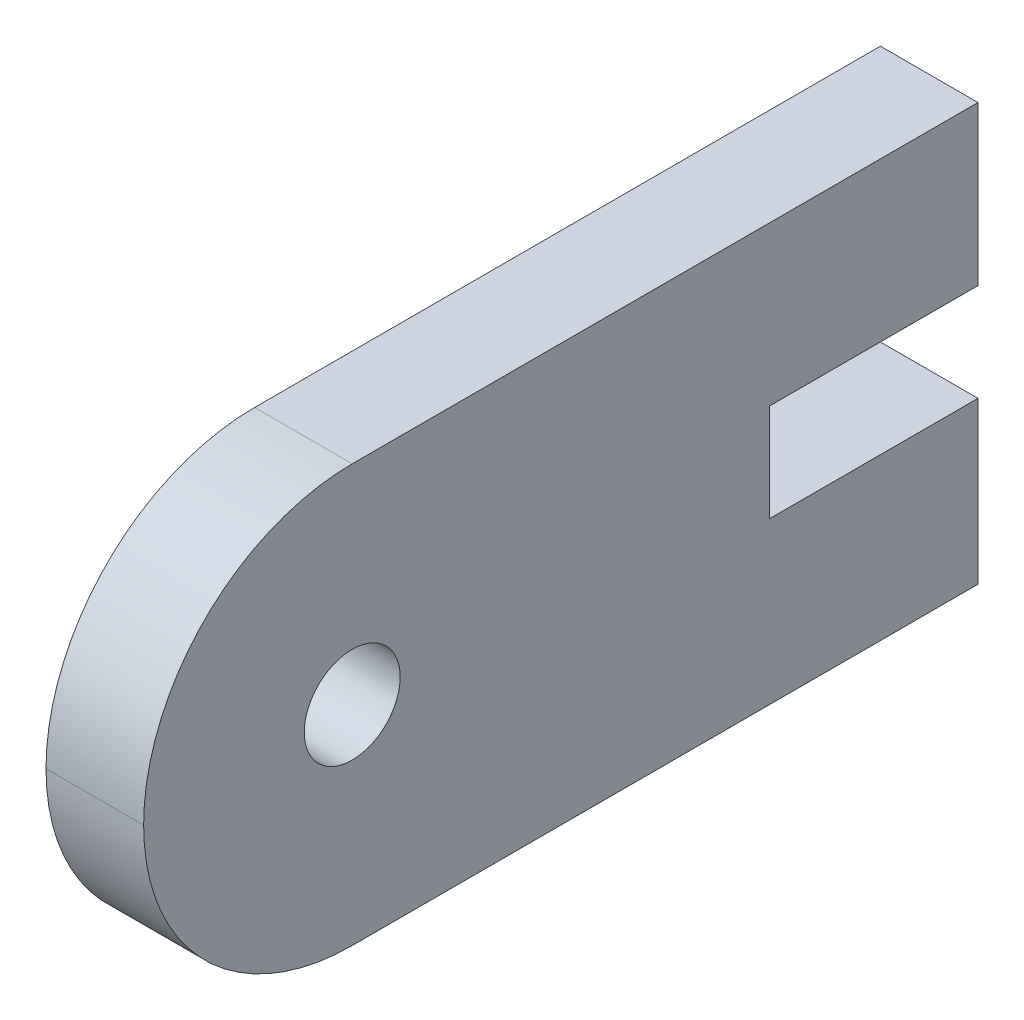
SolidWorks part; units mm, degrees
ref_plane "Front Plane" through (0, 0, 0) normal (1, 0, 0) x (0, 1, 0)
ref_plane "Top Plane" through (0, 0, 0) normal (0, 0, 1) x (0, 1, 0)
ref_plane "Right Plane" through (0, 0, 0) normal (0, 1, 0) x (-1, 0, 0)
sketch "Sketch1" plane through (0, 0, 0) normal (1, 0, 0) x (0, 1, 0)
  line L1 (-6.35, 12.7) -> (6.35, 12.7)
  line L2 (-6.35, 12.7) -> (-6.35, -12.7)
  line L3 (-6.35, -12.7) -> (6.35, -12.7)
  line L4 (6.35, 12.7) -> (6.35, -12.7)
  line L5 (-6.35, 12.7) -> (6.35, -12.7) construction
  line L6 (-6.35, -12.7) -> (6.35, 12.7) construction
  circle A0 centre (0, 6.35) radius 1.4605
  point P0 (0, 0)
  point P6 (-0.2148, -12.7)
  dimension "D1" = 2.921
  dimension "D2" = 12.7
  dimension "D3" = 25.4
  dimension "D4" = 6.35
extrude "Boss-Extrude1" add sketch "Sketch1" along normal blind 2.9718
sketch "Sketch2" plane through (2.9718, 0, 0) normal (1, 0, 0) x (0, 1, 0)
  line L0 (0, 102.9973) -> (0, -136.0454) construction
  line L5 (1.523, -12.7) -> (-1.4488, -12.7)
  line L6 (-6.35, -12.7) -> (6.35, -12.7) construction
  line L7 (-1.4488, -12.7) -> (-1.4488, -6.35)
  line L8 (-1.4488, -6.35) -> (1.523, -6.35)
  line L9 (1.523, -6.35) -> (1.523, -12.7)
  dimension "D1" = 2.9718
  dimension "D2" = 6.35
extrude "Cut-Extrude1" cut sketch "Sketch2" against normal through all
fillet "Fillet3" radius 6.35 2 edges at (1.4859, -6.35, 12.7) (1.4859, 6.35, 12.7)
